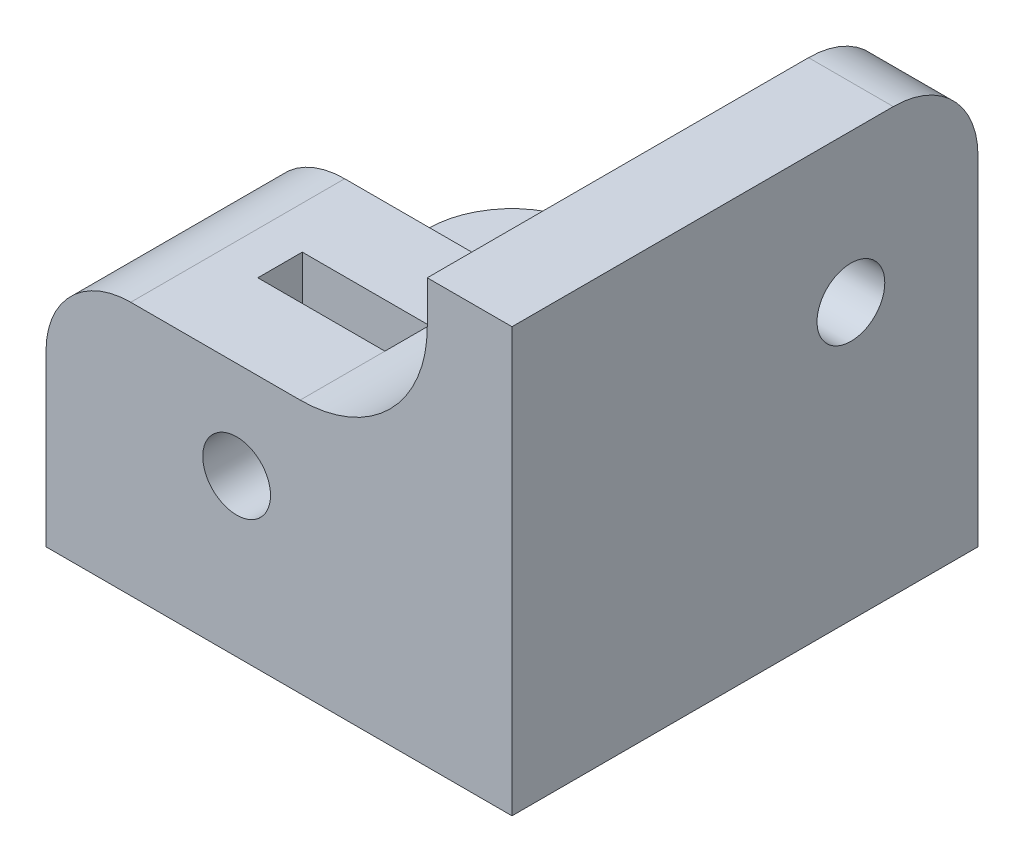
SolidWorks part; units mm, degrees
ref_plane "Front Plane" through (0, 0, 0) normal (0, 0, 1) x (1, 0, 0)
ref_plane "Top Plane" through (0, 0, 0) normal (0, 1, 0) x (1, 0, 0)
ref_plane "Right Plane" through (0, 0, 0) normal (1, 0, 0) x (0, 0, -1)
sketch "Sketch2" plane through (0, 0, 0) normal (0, 1, 0) x (1, 0, 0)
  line L0 (-9, 10.1) -> (9, 10.1)
  line L1 (-9, 0) -> (9, 0)
  line L2 (-9, 0) -> (-9, 22)
  line L3 (-9, 22) -> (9, 22)
  line L4 (9, 0) -> (9, 22)
  line L5 (3, 6.1) -> (-3, 6.1)
  line L6 (3, 6.1) -> (3, 4)
  line L7 (3, 4) -> (-3, 4)
  line L8 (-3, 6.1) -> (-3, 4)
  line L9 (3, 6.1) -> (-3, 4) construction
  line L10 (3, 4) -> (-3, 6.1) construction
  line L11 (9, 0) -> (13, 0)
  line L12 (9, 0) -> (9, 22)
  line L13 (9, 22) -> (13, 22)
  line L14 (13, 0) -> (13, 22)
  point P4 (0, 5.05)
  dimension "D1" = 4
  dimension "D2" = 2.1
  dimension "D3" = 6
  dimension "D4" = 18
  dimension "D5" = 22
  dimension "D6" = 4
  dimension "D7" = 4
extrude "Boss-Extrude1" add sketch "Sketch2" along normal blind 4 contours L1 L2 L3 L4 | L11 L14 L13 L12
extrude "Boss-Extrude2" add sketch "Sketch2<4>" along normal blind 12 contours L1 L4 L0 L2 L8 L5 L6 L7 region at (0, 0, -9.8936)
sketch "Sketch2<4>" plane through (0, 0, 0) normal (0, 1, 0) x (1, 0, 0) same geometry as "Sketch2"
extrude "Boss-Extrude3" add sketch "Sketch2<5>" along normal blind 20 contours L11 L14 L13 L4 region at (11, 0, -11)
sketch "Sketch2<5>" plane through (0, 0, 0) normal (0, 1, 0) x (1, 0, 0) same geometry as "Sketch2"
hole_wizard "Ø3.2 (3.2) Mount Holes" positions "3DSketch1" profile "Sketch3" hole size "Ø3.2" standard "ANSI Metric" end condition through all
sketch3d "3DSketch1"
  line L0 (-9, 0, 0) -> (13, 0, 0) construction
  line L1 (13, 20, 0) -> (13, 0, 0) construction
  line L2 (13, 0, 0) -> (13, 0, -22) construction
  point P0 (0, 7.4, 0)
  point P2 (0, 0, -16)
  point P4 (13, 13, -16)
  dimension "D2" = 16
  dimension "D1" = 16
  dimension "D3" = 7.4
  dimension "D4" = 13
sketch "Sketch3" plane through (0, 7.4, 0) normal (1, 0, 0) x (0, -1, 0)
  line L0 (0, 0) -> (0, 22)
  line L1 (0, 22) -> (1.6, 22)
  line L2 (1.6, 22) -> (1.6, 0)
  line L5 (1.6, 0) -> (0, 0)
  line L11 (0, -6.35) -> (0, 107.95) construction
  dimension "Thru Hole Dia." = 3.2
  dimension "Thru Hole Depth" = 22
fillet "Fillet2" radius 6 1 edges at (9, 12, -5.05)
fillet "Fillet1" radius 2 3 edges at (9, 4, -16.05) (0, 4, -10.1) (9, 11, -10.1)
fillet "Fillet3" radius 4 3 edges at (-9, 12, -5.05) (-9, 2, -22) (11, 20, -22)
equation "\"D2@3DSketch1\"=\"D1@3DSketch1\""
